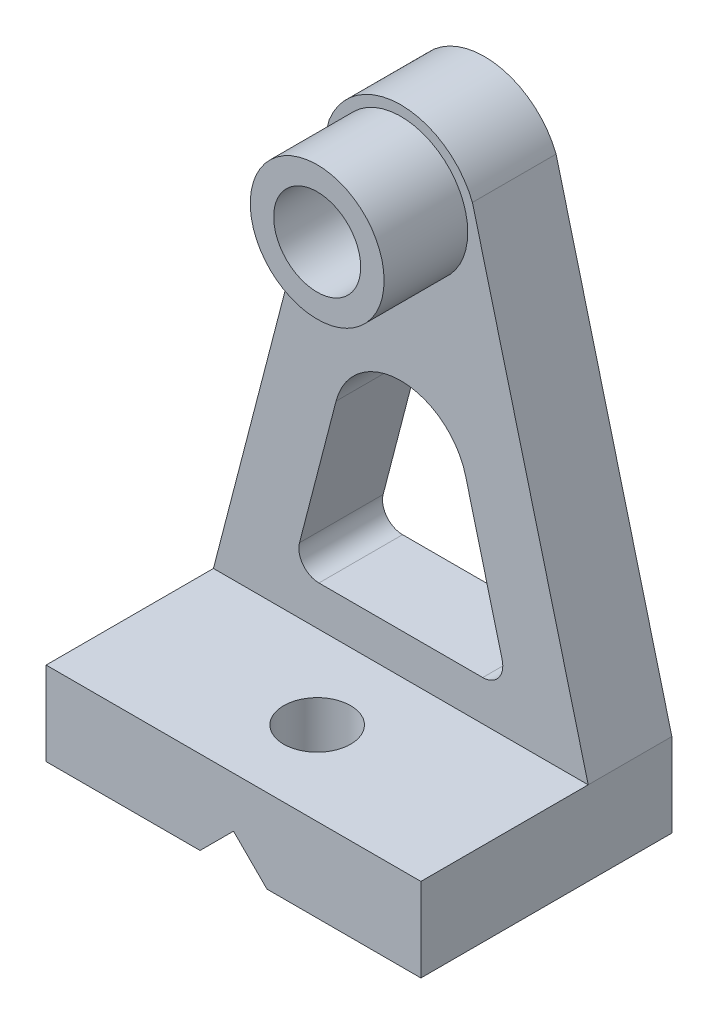
SolidWorks part; units mm, degrees
other "Kamera1"
ref_plane "Ön Düzlem" through (0, 0, 0) normal (0, 0, 1) x (1, 0, 0)
ref_plane "Üst Düzlem" through (0, 0, 0) normal (0, 1, 0) x (1, 0, 0)
ref_plane "Sağ Düzlem" through (0, 0, 0) normal (1, 0, 0) x (0, 0, -1)
sketch "Çizim1" plane through (0, 0, 0) normal (0, 0, 1) x (1, 0, 0)
  line L0 (-21.9839, 93.0719) -> (-56.5841, -40.3571)
  line L1 (20.8157, 93.0719) -> (55.4159, -40.3571)
  line L5 (-56.5841, -40.3571) -> (55.4159, -40.3571)
  circle A3 centre (-0.5841, 84.6429) radius 13
  circle A4 centre (-0.5841, 84.6429) radius 20
  arc A5 (20.8157, 93.0719) -> (-21.9839, 93.0719) centre (-0.5841, 84.6429) ccw
  circle A7 centre (-0.5841, 84.6429) radius 23 construction
  point P14 (22.4864, 88.0236)
  dimension "D1" = 125
  dimension "D2" = 137.8422
  dimension "D3" = 40
  dimension "D4" = 26
  dimension "D5" = 22.8305
  dimension "D6" = 3
  dimension "D7" = 112
extrude "Yükseklik-Ekstrüzyon1" add sketch "Çizim1" along normal blind 25 contours L1 A5 L0 L5 A4 | A4 A3 region at (-0.5841, 11.338, 0) region at (-20.0184, 84.6429, 0)
sketch "Çizim2" plane through (0, 0, 0) normal (1, 0, 0) x (0, 0, -1)
  line L1 (0, -40.3571) -> (-75, -40.3571)
  line L2 (0, -40.3571) -> (0, -65.3571)
  line L3 (0, -65.3571) -> (-75, -65.3571)
  line L4 (-75, -40.3571) -> (-75, -65.3571)
  dimension "D1" = 75
  dimension "D2" = 25
extrude "Yükseklik-Ekstrüzyon3" add sketch "Çizim2" against normal up to vertex (56.5841 mm away) and the other way up to vertex (55.4159 mm away) up to point (-56.5841, -40.3571, 0) other way up to point (55.4159, -40.3571, 0)
sketch "Çizim3" plane through (0, 0, 75) normal (0, 0, 1) x (1, 0, 0)
  line L0 (-0.5841, -65.3571) -> (-0.5841, -40.3571) construction
  line L2 (-56.5841, -65.3571) -> (55.4159, -65.3571) construction
  line L3 (-56.5841, -40.3571) -> (55.4159, -40.3571) construction
  line L4 (-10.5841, -65.3571) -> (-0.5841, -55.3571)
  line L5 (-0.5841, -55.3571) -> (9.4159, -65.3571)
  line L6 (-10.5841, -65.3571) -> (9.4159, -65.3571)
  dimension "D1" = 10
  dimension "D2" = 10
extrude "Kes-Ekstrüzyon1" cut sketch "Çizim3" against normal through all
sketch "Çizim5" plane through (0, -40.3571, 0) normal (0, 1, 0) x (1, 0, 0)
  line L0 (-0.5841, -25) -> (-0.5841, -75) construction
  line L1 (-56.5841, -25) -> (55.4159, -25) construction
  line L2 (-56.5841, -75) -> (55.4159, -75) construction
  circle A0 centre (-0.5841, -50) radius 10
  dimension "D1" = 20
extrude "Kes-Ekstrüzyon2" cut sketch "Çizim5" against normal through all
sketch "Çizim8" plane through (0, 0, 25) normal (0, 0, 1) x (1, 0, 0)
  line L0 (-0.5841, 107.6429) -> (-0.5841, -62.7542) construction
  line L19 (-2.6242, 88.0516) -> (-37.2244, -45.3773)
  line L20 (-19.9438, 21.2622) -> (-30.8644, -20.851)
  line L21 (-25.0565, -28.3571) -> (23.8883, -28.3571)
  line L22 (1.456, 88.0516) -> (36.0562, -45.3773)
  line L23 (18.7756, 21.2622) -> (29.6962, -20.851)
  line L24 (-56.5841, -40.3571) -> (55.4159, -40.3571) construction
  arc A0 (20.8157, 93.0719) -> (-21.9839, 93.0719) centre (-0.5841, 84.6429) ccw construction
  arc A1 (18.7756, 21.2622) -> (-19.9438, 21.2622) centre (-0.5841, 16.2419) ccw
  arc A2 (23.8883, -28.3571) -> (29.6962, -20.851) centre (23.8883, -22.3571) ccw
  arc A3 (-25.0565, -28.3571) -> (-30.8644, -20.851) centre (-25.0565, -22.3571) cw
  dimension "D4" = 40
  dimension "D5" = 6
  dimension "D3" = 12
  dimension "D1" = 20
  dimension "D2" = 20
extrude "Kes-Ekstrüzyon3" cut sketch "Çizim8" against normal through all
extrude "Yükseklik-Ekstrüzyon6" add sketch "Çizim1<7>" along normal blind 50 contours A4 | A3
sketch "Çizim1<7>" plane through (0, 0, 0) normal (0, 0, 1) x (1, 0, 0) same geometry as "Çizim1"
